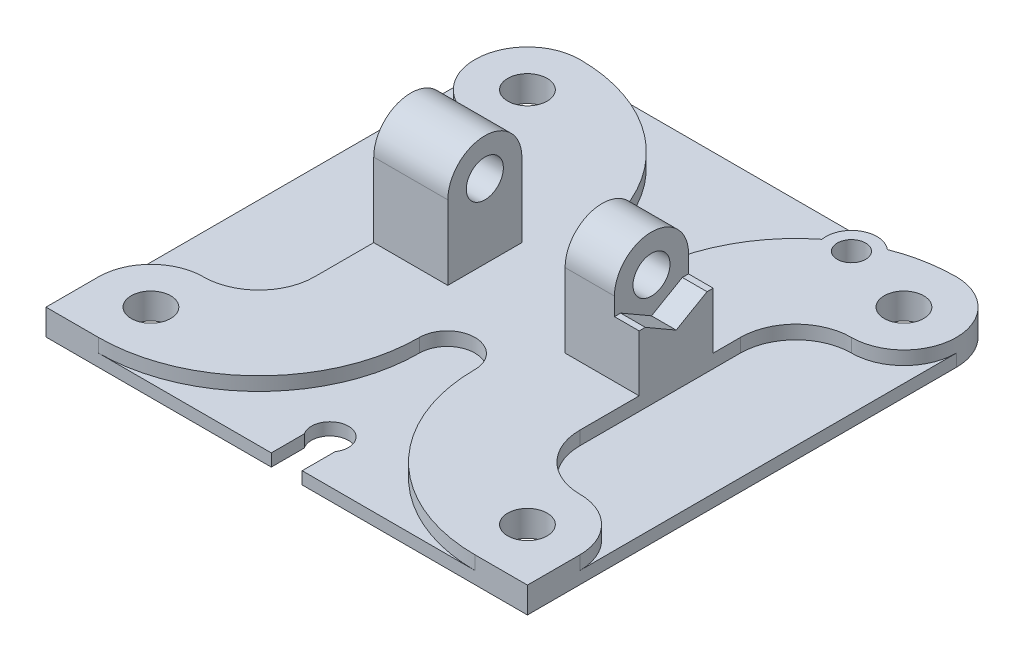
SolidWorks part; units mm, degrees
ref_plane "Front Plane" through (0, 0, 0) normal (0, 0, 1) x (1, 0, 0)
ref_plane "Top Plane" through (0, 0, 0) normal (0, 1, 0) x (1, 0, 0)
ref_plane "Right Plane" through (0, 0, 0) normal (1, 0, 0) x (0, 0, -1)
sketch "Sketch1" plane through (0, 0, 0) normal (0, 1, 0) x (1, 0, 0)
  line L0 (-19.5, 35.2) -> (-19.5, -19.5) construction
  line L1 (-19.5, 19.5) -> (19.5, 19.5)
  line L2 (-19.5, 19.5) -> (-19.5, -19.5)
  line L3 (-19.5, -19.5) -> (19.5, -19.5)
  line L4 (19.5, 19.5) -> (19.5, -19.5)
  line L5 (-19.5, 19.5) -> (19.5, -19.5) construction
  line L6 (-19.5, -19.5) -> (19.5, 19.5) construction
  line L7 (-19.5, -19.5) -> (19.5, -19.5) construction
  line L8 (0, -19.5) -> (0, 19.5) construction
  line L9 (-1.25, -19.5) -> (-1.25, -16.8292)
  line L10 (1.25, -19.5) -> (1.25, -16.8292)
  circle A0 centre (-15.25, -15.25) radius 1.6 construction
  circle A1 centre (15.25, -15.25) radius 1.6 construction
  circle A2 centre (9.2, 17.05) radius 1.15 construction
  circle A3 centre (15.25, 15.25) radius 1.6 construction
  circle A4 centre (-15.25, 15.25) radius 1.6 construction
  circle A5 centre (-15.25, -15.25) radius 1.6
  circle A6 centre (15.25, -15.25) radius 1.6
  circle A7 centre (9.2, 17.05) radius 1.15
  circle A8 centre (15.25, 15.25) radius 1.6
  circle A9 centre (-15.25, 15.25) radius 1.6
  circle A10 centre (-15.25, 15.25) radius 4.25
  circle A11 centre (15.25, 15.25) radius 4.25
  circle A12 centre (-15.25, -15.25) radius 4.25
  circle A13 centre (15.25, -15.25) radius 4.25
  circle A14 centre (0, -16) radius 1.5
  point P0 (0, 0)
  dimension "D1" = 3
  dimension "D2" = 3.5
  dimension "D3" = 2.5
extrude "Shape" add sketch "Sketch1" along normal blind 2.1 contours A13 L4 A11 L1 A10 L2 A12 L3 A7 | A10 A9 | A11 A8 | A13 A6 | A12 A5 | A12 L2 L3 | A13 L3 L4 region at (-0.0303, 0, -0.1136) region at (-12.3298, 0, -18.1702) region at (18.1702, 0, -18.1702) region at (-18.5507, 0, 18.5507) region at (-15.25, 0, 11.1202) region at (18.1702, 0, 18.1702) region at (18.5507, 0, 18.5507)
sketch "Sketch3" plane through (0, 2.1, 0) normal (0, 1, 0) x (1, 0, 0)
  line L0 (0, 19.5) -> (0, -19.5) construction
  line L1 (-15.25, 19.5) -> (15.25, 19.5) construction
  line L3 (-19.5, 1.3) -> (19.5, 1.3) construction
  line L4 (-19.5, 15.25) -> (-19.5, -19.5) construction
  line L5 (19.5, 15.25) -> (19.5, -19.5) construction
  line L6 (4.75, 4.3) -> (10.75, 4.3)
  line L7 (-4.75, 4.3) -> (-10.75, 4.3)
  line L8 (-4.75, 4.3) -> (-4.75, -1.7)
  line L9 (-4.75, -1.7) -> (-10.75, -1.7)
  line L10 (-10.75, 4.3) -> (-10.75, -1.7)
  line L11 (-4.75, 4.3) -> (-10.75, -1.7) construction
  line L12 (-4.75, -1.7) -> (-10.75, 4.3) construction
  line L13 (4.75, 4.3) -> (4.75, -1.7)
  line L14 (4.75, -1.7) -> (10.75, -1.7)
  line L15 (10.75, 4.3) -> (10.75, -1.7)
  line L16 (-19.5, -19.5) -> (19.5, -19.5) construction
  line L18 (10.75, 4.3) -> (10.75, -1.7)
  point P12 (-7.75, 1.3)
  dimension "D1" = 18.2
  dimension "D2" = 9.5
  dimension "D3" = 6
  dimension "D4" = 6
extrude "Supports" add sketch "Sketch3" along normal blind 9 contours L7 L10 L9 L8 | L15 L6 L13 L14 region at (7.75, 2.1, -1.3) region at (-7.75, 2.1, -1.3)
sketch "Sketch4" plane through (-10.75, 0, 0) normal (-1, 0, 0) x (0, 0, 1)
  line L0 (-1.3, 11.1) -> (-1.3, 2.1) construction
  line L2 (-4.3, 2.1) -> (1.7, 2.1) construction
  line L3 (1.7, 11.1) -> (1.7, 2.1) construction
  line L4 (-4.3, 11.1) -> (1.7, 11.1) construction
  circle A0 centre (-1.3, 8.1) radius 3
  circle A1 centre (-1.3, 8.1) radius 1.5
  line M2 (1.7, 2.1) -> (1.7, 11.1)
  line M4 (-4.3, 11.1) -> (-4.3, 2.1)
  line M11 (1.7, 11.1) -> (-4.3, 11.1)
  dimension "D1" = 3
extrude "Support cuts" cut sketch "Sketch4" against normal up to surface (21.5 mm away) contours A1 L0 | L0 A1 | A0 M11 M4 | A0 M2 M11 region at (-10.75, 10.4299, 1.0299) region at (-10.75, 10.4299, -3.6299) region at (-10.75, 8.1, -0.6634) region at (-10.75, 8.1, -1.9366) up to face at (10.75, 6.6, -1.3)
sketch "Sketch5" plane through (10.75, 0, 0) normal (1, 0, 0) x (0, 0, -1)
  line L0 (-1.2, 6.6566) -> (-1.7, 6.6566)
  line L1 (1.3, 5.2132) -> (3.8, 6.6566)
  line L2 (3.8, 6.6566) -> (3.8, 9.5434)
  line L3 (3.8, 9.5434) -> (1.3, 10.9868)
  line L4 (1.3, 10.9868) -> (-1.2, 9.5434)
  line L5 (-1.2, 9.5434) -> (-1.2, 6.6566)
  line L6 (-1.2, 6.6566) -> (1.3, 5.2132)
  line L7 (3.8, 6.6566) -> (4.3, 6.6566)
  line L8 (4.3, 2.1) -> (-1.7, 2.1) construction
  line L9 (-1.7, 8.1) -> (-1.7, 2.1) construction
  line L10 (4.3, 8.1) -> (4.3, 2.1) construction
  line L12 (-1.7, 8.1) -> (-1.7, 2.1)
  line L13 (-1.7, 2.1) -> (4.3, 2.1)
  line L14 (4.3, 2.1) -> (4.3, 8.1)
  circle A0 centre (1.3, 8.1) radius 2.5 construction
  arc A2 (4.3, 8.1) -> (-1.7, 8.1) centre (1.3, 8.1) ccw construction
  arc A3 (4.3, 8.1) -> (-1.7, 8.1) centre (1.3, 8.1) ccw
  dimension "D1" = 5
extrude "Nut holder" cut sketch "Sketch5" against normal blind 2 contours L5 L6 L1 L2 L3 L4 | L2 L7 L0 L5 L4 L3 region at (10.75, 6.7313, 1.45) region at (10.75, 8.1, -1.3)
sketch "Sketch6" plane through (-10.75, 0, 0) normal (-1, 0, 0) x (0, 0, 1)
  circle A0 centre (-1.3, 8.1) radius 1.95
  dimension "D1" = 3.9
extrude "Screw cut" cut sketch "Sketch6" against normal offset from surface (3.5 mm away) 18 up to face at (10.75, 5.1485, -1.3)
sketch "Sketch17" plane through (0, 2.1, 0) normal (0, 1, 0) x (1, 0, 0)
  line L0 (-19.5, 15.25) -> (-19.5, -19.5) construction
  line L1 (10.75, 6.5) -> (10.75, -6.5)
  line L2 (-15.25, 19.5) -> (-15.25, 11) construction
  line L3 (-15.25, -11) -> (-15.25, -19.5) construction
  line L4 (-10.75, 4.3) -> (-10.75, 6.5)
  line L5 (-10.75, -1.7) -> (-10.75, -6.5)
  line L6 (0, 19.5) -> (0, -14.5) construction
  line L7 (-15.25, 19.5) -> (15.25, 19.5) construction
  line L8 (-10.75, -6.5) -> (0, -6.5) construction
  line L9 (-10.75, 6.5) -> (0, 6.5) construction
  line L10 (-10.75, 4.3) -> (-10.75, -1.7)
  line L16 (1.25, -16.8292) -> (1.25, -19.5)
  line L17 (1.25, -19.5) -> (19.5, -19.5)
  line L18 (19.5, -19.5) -> (19.5, 15.25)
  line L19 (15.25, 19.5) -> (-15.25, 19.5)
  line L20 (-19.5, 15.25) -> (-19.5, -19.5)
  line L21 (-19.5, -19.5) -> (-1.25, -19.5)
  line L22 (-1.25, -19.5) -> (-1.25, -16.8292)
  line L23 (1.25, -16.8292) -> (1.25, -19.5)
  line L24 (1.25, -19.5) -> (19.5, -19.5)
  line L25 (19.5, -19.5) -> (19.5, 15.25)
  line L26 (15.25, 19.5) -> (-15.25, 19.5)
  line L27 (-19.5, 15.25) -> (-19.5, -19.5)
  line L28 (-19.5, -19.5) -> (-1.25, -19.5)
  line L29 (-1.25, -19.5) -> (-1.25, -16.8292)
  circle A0 centre (-15.25, 15.25) radius 4.25
  arc A1 (-15.25, 19.5) -> (-19.5, 15.25) centre (-15.25, 15.25) ccw construction
  arc A2 (-15.25, 11) -> (-10.75, 6.5) centre (-15.25, 6.5) cw
  arc A3 (-15.25, -11) -> (-10.75, -6.5) centre (-15.25, -6.5) ccw
  circle A4 centre (-15.25, -15.25) radius 4.25
  circle A5 centre (15.25, -15.25) radius 4.25
  arc A6 (-15.25, -19.5) -> (-2.25, -6.5) centre (-15.25, -6.5) ccw
  arc A7 (1.25, -16.8292) -> (-1.25, -16.8292) centre (0, -16) ccw construction
  circle A8 centre (0, -6.5) radius 2.25
  arc A9 (-15.25, 19.5) -> (-2.25, 6.5) centre (-15.25, 6.5) cw
  circle A10 centre (0, 6.5) radius 2.25
  arc A11 (15.25, -19.5) -> (2.25, -6.5) centre (15.25, -6.5) cw
  arc A12 (15.25, -11) -> (10.75, -6.5) centre (15.25, -6.5) cw
  arc A13 (1.25, -16.8292) -> (-1.25, -16.8292) centre (0, -16) ccw
  arc A14 (19.5, 15.25) -> (15.25, 19.5) centre (15.25, 15.25) ccw
  arc A15 (-15.25, 19.5) -> (-19.5, 15.25) centre (-15.25, 15.25) ccw
  arc A16 (1.25, -16.8292) -> (-1.25, -16.8292) centre (0, -16) ccw
  arc A17 (19.5, 15.25) -> (15.25, 19.5) centre (15.25, 15.25) ccw
  arc A18 (-15.25, 19.5) -> (-19.5, 15.25) centre (-15.25, 15.25) ccw
  arc A19 (15.25, 19.5) -> (2.25, 6.5) centre (15.25, 6.5) ccw
  arc A20 (15.25, 11) -> (10.75, 6.5) centre (15.25, 6.5) ccw
  circle A21 centre (15.25, 15.25) radius 4.25
  circle A22 centre (9.2, 17.05) radius 2.0621
  line M16 (10.75, 4.3) -> (10.75, -1.7)
  arc M20 (-1.25, -16.8292) -> (1.25, -16.8292) centre (0, -16) cw
  line M21 (1.25, -16.8292) -> (1.25, -19.5)
  line M22 (1.25, -19.5) -> (19.5, -19.5)
  line M25 (15.25, 19.5) -> (-15.25, 19.5)
  line M27 (-19.5, 15.25) -> (-19.5, -19.5)
  line M29 (-1.25, -19.5) -> (-1.25, -16.8292)
  circle M30 centre (9.2, 17.05) radius 1.15
  line M35 (-10.75, -1.7) -> (-10.75, 4.3)
  dimension "D1" = 0
extrude "Cut-Extrude1" cut sketch "Sketch17" against normal offset from surface (1.1 mm away) 1 contours A4 A3 L5 L4 A2 A0 M35 M27 | A19 A9 A10 M25 M30 | A11 A8 A6 L28 M22 M29 M20 M21 | L25 A21 A20 L1 A12 A5 M16 | A8 | A10 region at (15.4165, 2.1, 0) region at (-0.2501, 2.1, -15.3982) region at (8.25, 2.1, 19.1685) region at (0, 2.1, -6.5) region at (0, 2.1, 6.5) region at (-15.4165, 2.1, 0) up to face at (0, 0, 3.8069)
sketch "Sketch9" plane through (0, 2.1, 0) normal (0, 1, 0) x (1, 0, 0)
  line L0 (8, 4.5) -> (8, 24) construction
  line L1 (8, 24) -> (-8, 24) construction
  line L2 (-8, 24) -> (-8, 4.5) construction
  line L3 (8, 4.5) -> (8, 24)
  line L4 (8, 24) -> (-8, 24)
  line L5 (-8, 24) -> (-8, 4.5)
  line L6 (-15.25, 19.5) -> (15.25, 19.5) construction
  line L7 (-15.25, 19.5) -> (15.25, 19.5)
  line L8 (-8, 24) -> (8, 19.5) construction
  line L9 (-8, 24) -> (8, 24)
  line L14 (10, 25) -> (-10, 25)
  line L15 (10, 25) -> (10, 18.5)
  line L16 (10, 18.5) -> (-10, 18.5)
  line L17 (-10, 25) -> (-10, 18.5)
  line L18 (10, 25) -> (-10, 18.5) construction
  line L19 (10, 18.5) -> (-10, 25) construction
  point P10 (0, 21.75)
  dimension "D1" = 1
  dimension "D2" = 2
extrude "Datalogger front" [suppressed] add sketch "Sketch9" against normal up to surface (2.1 mm away) up to face at (0, 0, 3.8069)
sketch "Sketch10" [suppressed] plane through (0, 0, -25) normal (0, 0, -1) x (-1, 0, 0)
  line L1 (-8, 2.1) -> (8, 2.1)
  line L2 (-8, 2.1) -> (-8, 1)
  line L3 (-8, 1) -> (8, 1)
  line L4 (8, 2.1) -> (8, 1)
  line L6 (-8, 1) -> (8, 1) construction
  line L8 (8, 2.1) -> (8, 1) construction
extrude "Datalogger main cut" [suppressed] cut sketch "Sketch10" against normal offset from surface (20.7 mm away) 0.2 offset beyond the face yes
sketch "Sketch11" [suppressed] plane through (0, 1, 0) normal (0, 1, 0) x (1, 0, 0)
  line L6 (-7.5, 22.5) -> (7.5, 22.5)
  line L9 (8, 25) -> (-8, 25) construction
  line L12 (-7.5, 4.8) -> (-0.4153, 4.8)
  line L13 (7.5, 19) -> (7.5, 24.5)
  line L14 (7.5, 24.5) -> (-7.5, 24.5)
  line L15 (7.5, 24.5) -> (-7.5, 24.5)
  line L17 (-7.5, 17.5538) -> (-7.5, 4.8)
  line L18 (-7.5, 4.8) -> (-0.4153, 4.8)
  line L19 (7.5, 19) -> (7.5, 24.5)
  line L20 (0.4153, 4.8) -> (7.5, 4.8)
  line L21 (0.4153, 4.8) -> (7.5, 4.8)
  line L22 (7.5, 4.8) -> (7.5, 18.9668)
  line L23 (-7.5, 17.5538) -> (-7.5, 4.8)
  line L24 (7.5, 4.8) -> (7.5, 18.9668)
  line L25 (7.5381, 19) -> (7.5, 19)
  line L26 (7.5381, 19) -> (7.5, 19)
  line L27 (-7.5, 24.5) -> (-7.5, 19)
  line L28 (-7.5, 24.5) -> (-7.5, 19)
  line L29 (-7.5, 19) -> (-10, 19)
  line L30 (-7.5, 19) -> (-10, 19)
  line L31 (-10, 19) -> (-10.151, 19)
  line L32 (-10, 19) -> (-10.151, 19)
  arc A4 (-7.5, 17.5538) -> (-10.151, 19) centre (-15.25, 6.5) ccw
  arc A5 (-7.5, 17.5538) -> (-10.151, 19) centre (-15.25, 6.5) ccw
  arc A6 (-0.4153, 4.8) -> (0.4153, 4.8) centre (0, 6.5) ccw
  arc A7 (-0.4153, 4.8) -> (0.4153, 4.8) centre (0, 6.5) ccw
  arc A8 (7.5381, 19) -> (7.5, 18.9668) centre (9.2, 17.05) ccw
  arc A9 (7.5381, 19) -> (7.5, 18.9668) centre (9.2, 17.05) ccw
  dimension "D2" = 2.5
  dimension "D1" = 0.5
extrude "Datalogger bottom cut" [suppressed] cut sketch "Sketch11" against normal up to next
sketch "Sketch12" [suppressed] plane through (0, 1, 0) normal (0, 1, 0) x (1, 0, 0)
  line L1 (-8, 25) -> (8, 25)
  line L2 (-8, 25) -> (-8, 24)
  line L3 (-8, 24) -> (8, 24)
  line L4 (8, 25) -> (8, 24)
  dimension "D1" = 1
extrude "Datalogger front retainer" [suppressed] add sketch "Sketch12" along normal up to surface (1.1 mm away) up to face at (15.25, 2.1, 16.85)
sketch "Sketch13" [suppressed] plane through (0, 2.1, 0) normal (0, 1, 0) x (1, 0, 0)
  line L1 (-8, 4.3) -> (-9.25, 4.3)
  line L2 (-8, 4.3) -> (-8, 7.3)
  line L3 (-8, 7.3) -> (-9.25, 7.3)
  line L4 (-9.25, 4.3) -> (-9.25, 7.3)
  line L5 (-8, 7.3) -> (-7.75, 7.3)
  line L6 (-8, 7.3) -> (-8, 4.3)
  line L7 (-8, 4.3) -> (-7.75, 4.3)
  line L8 (-7.75, 7.3) -> (-7.75, 4.3)
  line L9 (0, 7.608) -> (0, -4.6396) construction
  line L10 (9.25, 4.3) -> (9.25, 7.3)
  line L11 (8, 7.3) -> (9.25, 7.3)
  line L12 (8, 7.3) -> (7.75, 7.3)
  line L13 (7.75, 7.3) -> (7.75, 4.3)
  line L14 (8, 4.3) -> (7.75, 4.3)
  line L15 (8, 4.3) -> (9.25, 4.3)
  dimension "D1" = 1.5
  dimension "D2" = 3
  dimension "D3" = 0.25
extrude "Datalogger rear retainers" [suppressed] add sketch "Sketch13" along normal blind 1
sketch "Sketch14" [suppressed] plane through (0, 2.1, 0) normal (0, 1, 0) x (1, 0, 0)
  line L0 (-15.25, 19.5) -> (-10, 19.5) construction
  line L1 (-10, 25) -> (-7.75, 25)
  line L2 (-10, 25) -> (-10, 19.5)
  line L3 (-10, 19.5) -> (-7.75, 19.5)
  line L4 (-7.75, 25) -> (-7.75, 19.5)
  line L5 (-8, 4.3) -> (-8, 17.2906) construction
  line L6 (-19.5, -19.5) -> (19.5, -19.5) construction
  line L8 (0, 25) -> (0, -19.5) construction
  line L9 (10, 25) -> (-10, 25) construction
  line L11 (10, 25) -> (10, 19.5)
  line L12 (10, 25) -> (7.75, 25)
  line L13 (7.75, 25) -> (7.75, 19.5)
  line L14 (10, 19.5) -> (7.75, 19.5)
  dimension "D1" = 0.25
extrude "Datalogger side retainers" [suppressed] add sketch "Sketch14" along normal up to surface (1 mm away) up to face at (15.25, 2.1, 16.85)
sketch "Sketch15" [suppressed] plane through (0, 0, -25) normal (0, 0, -1) x (-1, 0, 0)
  line L0 (-7.75, 2.6) -> (-8.25, 3.1)
  line L2 (-7.75, 3.1) -> (-7.75, 2.1) construction
  line L3 (-8.25, 3.1) -> (-7.75, 3.1)
  line L4 (-7.75, 3.1) -> (-7.75, 2.6)
  line L5 (0, 0) -> (0, 2.1) construction
  line L6 (-7.75, 2.1) -> (7.75, 2.1) construction
  line L7 (8.25, 3.1) -> (7.75, 3.1)
  line L8 (7.75, 3.1) -> (7.75, 2.6)
  line L9 (7.75, 2.6) -> (8.25, 3.1)
  dimension "D1" = 45
extrude "Datalogger side retainer clips" [suppressed] cut sketch "Sketch15" against normal up to next
sketch "Sketch16" [suppressed] plane through (0, 2.1, 0) normal (0, 1, 0) x (1, 0, 0)
  line L0 (-19.5, -15.25) -> (-19.5, -19.5) construction
  line L1 (-15.25, 11) -> (-15.25, -11) construction
  line L2 (0, -2.4485) -> (-4.0515, -2.4485) construction
  line L3 (0, 25) -> (0, -19.5) construction
  line L4 (7.75, 25) -> (-7.75, 25) construction
  line L5 (-19.5, -19.5) -> (-15.25, -19.5) construction
  line L6 (-15.25, -11) -> (0, -11) construction
  line L7 (-11, -15.25) -> (0, -15.25) construction
  line L8 (-4.0515, 25) -> (-4.0515, -19.5) construction
  line L9 (-10.75, 4.3) -> (-10.75, -1.7) construction
  line L10 (-10.75, 6.5) -> (-10.75, 19.5) construction
  line L11 (-10, 19.5) -> (-8, 19.5) construction
  line L12 (-19.5, 15.25) -> (-19.5, -15.25)
  line L13 (-10.75, -1.7) -> (-10.75, -11) construction
  line L14 (-10.75, -6.5) -> (0, -6.5) construction
  line L15 (-15.25, 11) -> (-10.75, 11) construction
  line L16 (-10.75, 6.5) -> (-10.75, -6.5)
  line L17 (-4.75, -1.7) -> (-10.75, -1.7) construction
  line L18 (10.75, 6.5) -> (10.75, -6.5)
  line L19 (-15.25, -19.5) -> (15.25, -19.5)
  circle A0 centre (-15.25, 15.25) radius 4.25
  circle A1 centre (-15.25, -15.25) radius 4.25
  arc A2 (-15.25, 19.5) -> (-15.25, 11) centre (-15.25, 15.25) ccw construction
  arc A3 (-15.25, 11) -> (-10.75, 6.5) centre (-15.25, 6.5) cw
  arc A4 (-15.25, -11) -> (-10.75, -6.5) centre (-15.25, -6.5) ccw
  arc A5 (-11, -15.25) -> (-7.625, -11) centre (-6.6366, -15.25) cw
  arc A6 (-7.625, -11) -> (-4.0515, -6.5) centre (-8.6716, -6.5) ccw
  arc A7 (-4.0515, -6.5) -> (4.0515, -6.5) centre (0, -6.5) cw
  arc A8 (7.625, -11) -> (4.0515, -6.5) centre (8.6716, -6.5) cw
  arc A9 (11, -15.25) -> (7.625, -11) centre (6.6366, -15.25) ccw
  circle A10 centre (15.25, -15.25) radius 4.25
  arc A11 (15.25, -11) -> (10.75, -6.5) centre (15.25, -6.5) cw
  arc A12 (15.25, 11) -> (10.75, 6.5) centre (15.25, 6.5) ccw
  circle A13 centre (15.25, 15.25) radius 4.25
extrude "Weight cut" [suppressed] cut sketch "Sketch16" against normal offset from surface (1.1 mm away) 1 up to face at (0, 0, 3.8069)
fillet "Fillets" [suppressed] radius 2
fillet "Fillet2" [suppressed] radius 1
